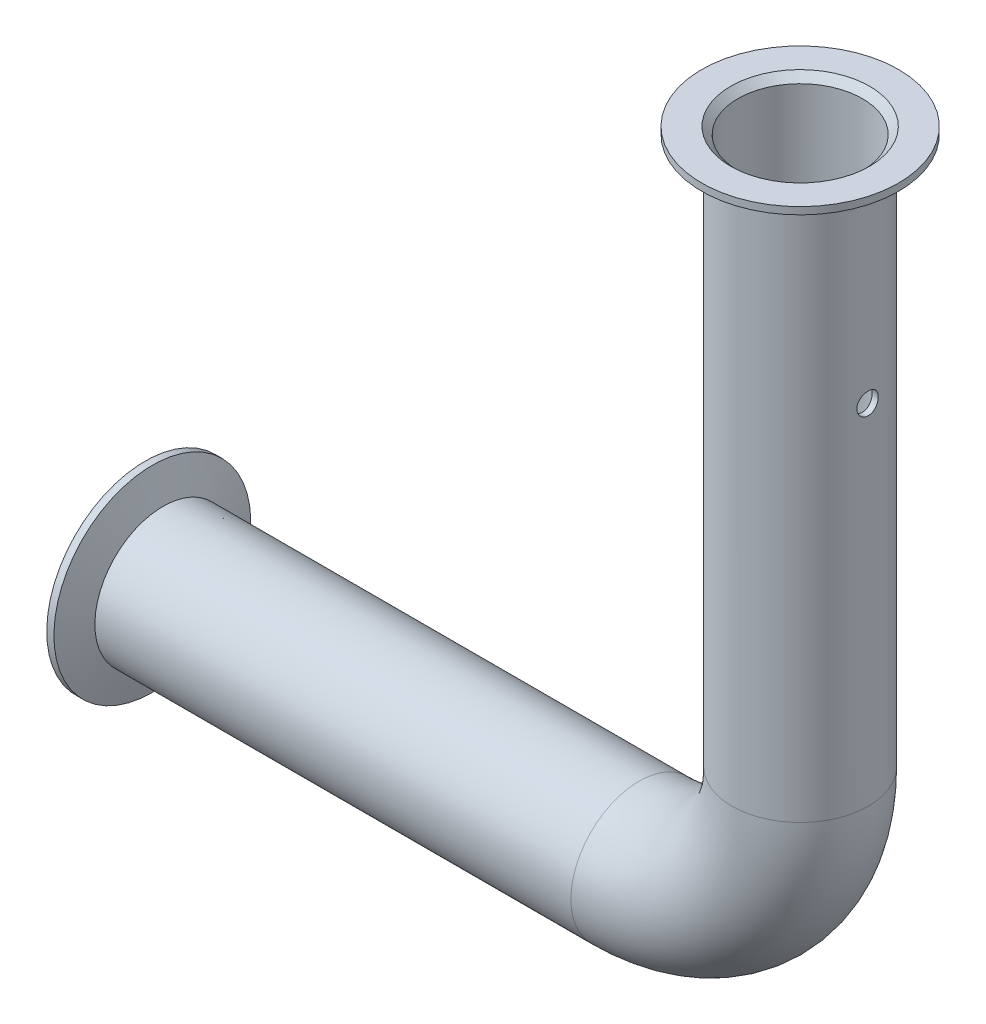
SolidWorks part; units mm, degrees
note: The reader was unsure of these and kept them because the rebuilt part matched: shared geometry of "스케치2<2>", "스케치1<2>".
ref_plane "정면" through (0, 0, 0) normal (0, 0, 1) x (1, 0, 0)
ref_plane "윗면" through (0, 0, 0) normal (0, 1, 0) x (1, 0, 0)
ref_plane "우측면" through (0, 0, 0) normal (1, 0, 0) x (0, 0, -1)
sketch "스케치1" plane through (0, 0, 0) normal (0, 0, 1) x (1, 0, 0)
  line L0 (0, 0) -> (133, 0)
  line L1 (178, 45) -> (178, 195)
  arc A0 (133, 0) -> (178, 45) centre (133, 45) ccw
  dimension "D3" = 45
  dimension "D1" = 195
  dimension "D2" = 178
sketch "스케치2" plane through (0, 0, 0) normal (1, 0, 0) x (0, 0, -1)
  circle A0 centre (0, 0) radius 19.05
  circle A1 centre (0, 0) radius 17.4
  dimension "D1" = 38.1
  dimension "D2" = 34.8
sweep "스윕1" add profiles "스케치2" path "스케치1"
sweep "스윕2" add profiles "스케치2<2>" path "스케치1<2>"
sketch "스케치2<2>" plane through (0, 0, 0) normal (1, 0, 0) x (0, 0, -1) same geometry as "스케치2"
sketch "스케치1<2>" plane through (0, 0, 0) normal (0, 0, 1) x (1, 0, 0) same geometry as "스케치1"
sketch "스케치4" plane through (0, 0, 0) normal (0, 0, 1) x (1, 0, 0)
  line L0 (0, 0) -> (0, 19.05)
  line L1 (0, 19.05) -> (-3, 27.5)
  line L3 (-5, 0) -> (0, 0)
  line L4 (-5, 27.5) -> (-5, 0)
  line L5 (-5, 27.5) -> (-3, 27.5)
  dimension "D1" = 27.5
  dimension "D2" = 2
  dimension "D3" = 3
revolve "회전1" add sketch "스케치4" angle 360 about L3
sketch "스케치5" plane through (0, 0, 0) normal (0, 0, 1) x (1, 0, 0)
  line L0 (178, 195) -> (178, 200)
  line L1 (197.05, 195) -> (158.95, 195) construction
  line L2 (178, 200) -> (205.5, 200)
  line L3 (205.5, 200) -> (205.5, 198)
  line L4 (205.5, 198) -> (197.05, 195)
  line L5 (197.05, 195) -> (178, 195)
  dimension "D1" = 2
  dimension "D2" = 5
  dimension "D3" = 27.5
revolve "회전2" add sketch "스케치5" angle 360 about L0
sketch "스케치6" plane through (-5, 0, 0) normal (-1, 0, 0) x (0, 0, 1)
  circle A0 centre (0, 0) radius 17.4
  dimension "D1" = 34.8
extrude "컷-돌출1" cut sketch "스케치6" against normal up to next
sketch "스케치7" plane through (0, 200, 0) normal (0, 1, 0) x (1, 0, 0)
  circle A0 centre (178, 0) radius 17.4
  dimension "D1" = 34.8
extrude "컷-돌출2" cut sketch "스케치7" against normal up to next
chamfer "모따기1" distance 2 angle 45 2 edges at (-5, -17.4, 0) (178, 200, 17.4)
sketch "스케치8" plane through (0, 0, 0) normal (1, 0, 0) x (0, 0, -1)
  line L0 (19.4, 200) -> (-19.4, 200) construction
  circle A0 centre (0, 142.5) radius 3
  dimension "D1" = 6
  dimension "D2" = 57.5
extrude "컷-돌출3" cut sketch "스케치8" against normal through all both and the other way through all
